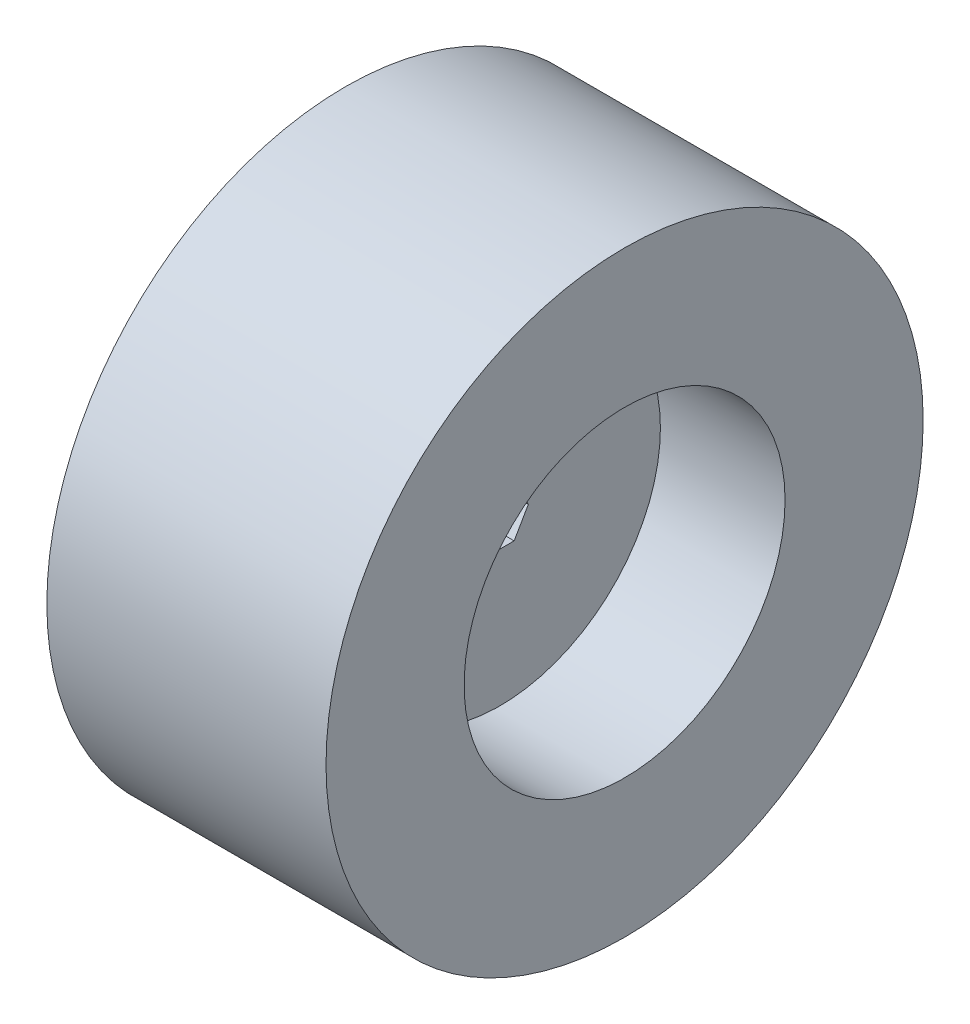
SolidWorks part; units mm, degrees
ref_plane "前视基准面" through (0, 0, 0) normal (0, 0, 1) x (1, 0, 0)
ref_plane "上视基准面" through (0, 0, 0) normal (0, 1, 0) x (1, 0, 0)
ref_plane "右视基准面" through (0, 0, 0) normal (1, 0, 0) x (0, 0, -1)
other "Configuration Table"
sketch "Sketch1" plane through (0, 0, 0) normal (1, 0, 0) x (0, 0, -1)
  line L1 (3.81, 0) -> (1.905, 3.2996)
  line L2 (1.905, 3.2996) -> (-1.905, 3.2996)
  line L3 (-1.905, 3.2996) -> (-3.81, 0)
  line L4 (-3.81, 0) -> (-1.905, -3.2996)
  line L5 (-1.905, -3.2996) -> (1.905, -3.2996)
  line L6 (1.905, -3.2996) -> (3.81, 0)
  circle A0 centre (0, 0) radius 40
  circle A1 centre (0, 0) radius 3.2996 construction
  circle A2 centre (0, 0) radius 21.5
  circle A3 centre (0, 0) radius 1.5
  dimension "D1" = 80
  dimension "D3" = 43
  dimension "D4" = 3
  dimension "D2" = 7.62
extrude "Boss-Extrude1" add sketch "Sketch1" along normal blind 37.4 contours A0 A2 region at (0, 0, 38.8686)
extrude "Boss-Extrude2" add sketch "Sketch1<3>" along normal blind 20.7 contours A2 L6 L5 L4 L3 L2 L1 region at (0, 0, 20.8919)
sketch "Sketch1<3>" plane through (0, 0, 0) normal (1, 0, 0) x (0, 0, -1) same geometry as "Sketch1"
extrude "Boss-Extrude3" add sketch "Sketch1<5>" along normal blind 10.45 contours L5 L6 L1 L2 L3 L4 A3 region at (0, -1.5994, -2.7702)
sketch "Sketch1<5>" plane through (0, 0, 0) normal (1, 0, 0) x (0, 0, -1) same geometry as "Sketch1"
